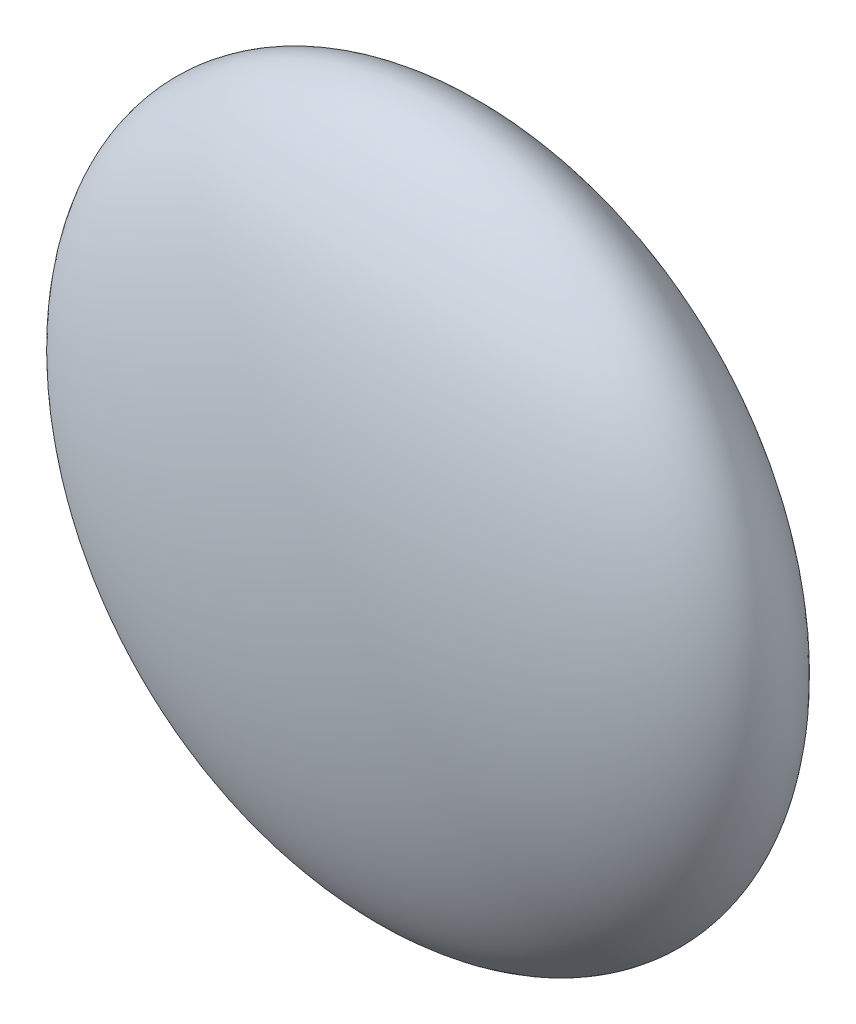
SolidWorks part; units mm, degrees
ref_plane "Front Plane" through (0, 0, 0) normal (0, 0, 1) x (1, 0, 0)
ref_plane "Top Plane" through (0, 0, 0) normal (0, 1, 0) x (1, 0, 0)
ref_plane "Right Plane" through (0, 0, 0) normal (1, 0, 0) x (0, 0, -1)
sketch "Sketch1" plane through (0, 0, 0) normal (1, 0, 0) x (0, 0, -1)
  line L0 (-0.242, 0) -> (0.242, 0)
  line L1 (0, 0.625) -> (0, -0.625) construction
  ellipse E0 centre (0, 0) end of major axis (0, 0.625) minor radius 0.242 (-0.242, 0) -> (0.242, 0) cw
  dimension "D1" = 0.484
  dimension "D2" = 1.25
revolve "Revolve1" add sketch "Sketch1" angle 360 about L0
ref_axis "Axis1" through (0, 0.6875, 0) along (0, -1, 0)
ref_axis "Axis2" through (0.6875, 0, 0) along (-1, 0, 0)
